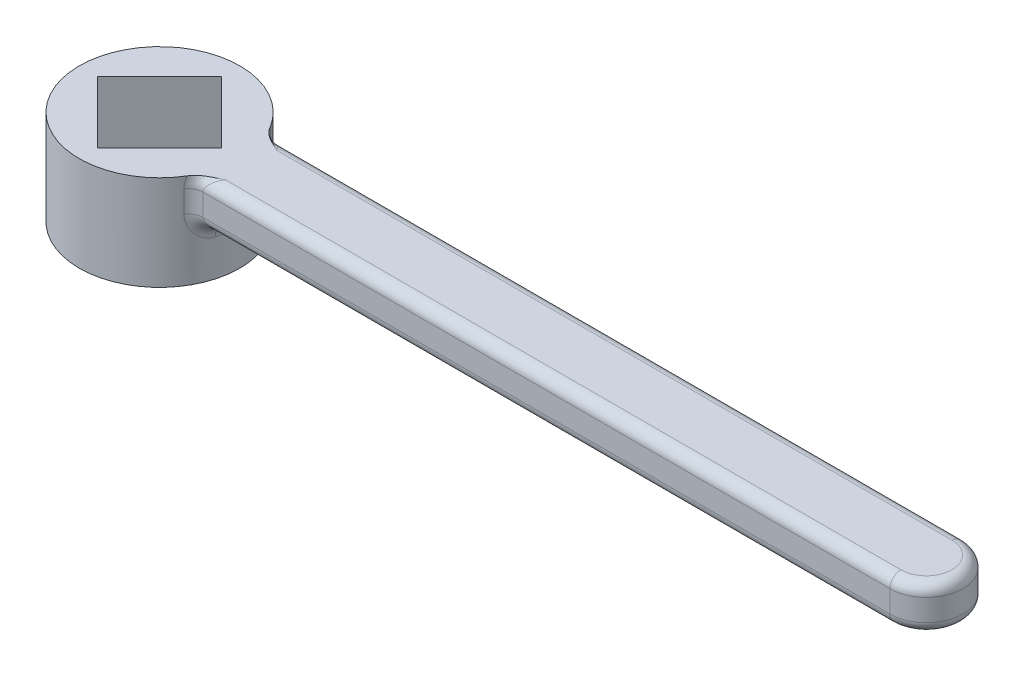
SolidWorks part; units mm, degrees
ref_plane "前视基准面" through (0, 0, 0) normal (0, 0, 1) x (1, 0, 0)
ref_plane "上视基准面" through (0, 0, 0) normal (0, 1, 0) x (1, 0, 0)
ref_plane "右视基准面" through (0, 0, 0) normal (1, 0, 0) x (0, 0, -1)
sketch "草图1" plane through (0, 0, 0) normal (0, 1, 0) x (1, 0, 0)
  circle A0 centre (0, 0) radius 11
  dimension "D2" = 22
extrude "拉伸1" add sketch "草图1" along normal blind 13
sketch "草图2" plane through (0, 13, 0) normal (0, 1, 0) x (1, 0, 0)
  line L0 (0, 0) -> (81.3721, 0) construction
  line L1 (105, 5) -> (9.798, 5)
  line L2 (105, -5) -> (9.798, -5)
  arc A0 (105, -5) -> (105, 5) centre (105, 0) ccw
  circle A1 centre (0, 0) radius 11 construction
  arc A2 (9.798, -5) -> (9.798, 5) centre (0, 0) ccw
  dimension "D1" = 10
  dimension "D2" = 110
extrude "拉伸2" add sketch "草图2" against normal blind 6
fillet "圆角1" radius 1.5 6 edges at (57.399, 7, -5) (110, 7, 0) (57.399, 13, -5) (110, 13, 0) (57.399, 7, 5) (57.399, 13, 5)
fillet "圆角2" radius 2 7 edges at (10.0449, 12.6328, -4.4833) (9.798, 10, -5) (9.9338, 7.6333, -4.7243) (11, 7, 0) (10.0449, 7.3672, 4.4833) (9.798, 10, 5) (9.9338, 12.3667, 4.7243)
sketch "草图3" plane through (0, 13, 0) normal (0, 1, 0) x (1, 0, 0)
  line L0 (-8.4853, 0) -> (0, 8.4853)
  line L1 (-8.4853, 0) -> (0, -8.4853)
  line L2 (0, 8.4853) -> (8.4853, 0)
  line L3 (0, -8.4853) -> (8.4853, 0)
  line L4 (-8.4853, 0) -> (8.4853, 0) construction
  line L5 (0, 8.4853) -> (0, -8.4853) construction
  dimension "D2" = 12
extrude "拉伸3" cut sketch "草图3" against normal up to next
